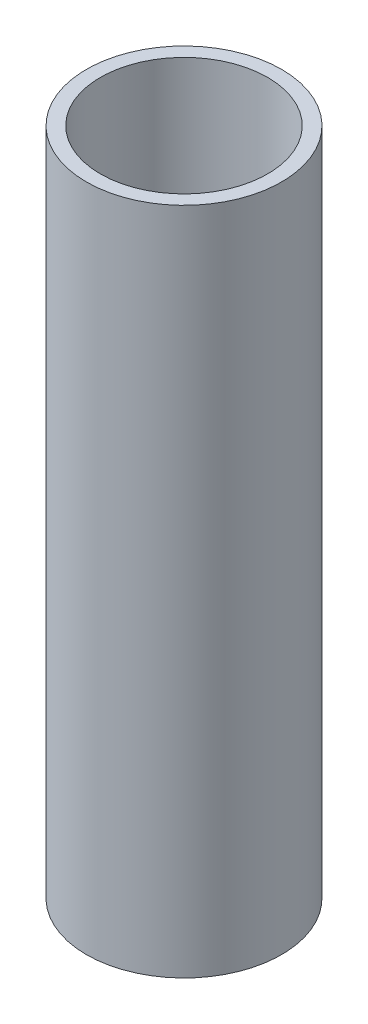
SolidWorks part; units mm, degrees
material "S-Glass Fiber"
ref_plane "Front Plane" through (0, 0, 0) normal (0, 0, 1) x (1, 0, 0)
ref_plane "Top Plane" through (0, 0, 0) normal (0, 1, 0) x (1, 0, 0)
ref_plane "Right Plane" through (0, 0, 0) normal (1, 0, 0) x (0, 0, -1)
sketch "Sketch1" plane through (0, 0, 0) normal (0, 0, 1) x (1, 0, 0)
  line L0 (0, 0) -> (0, -152.4) construction
  line L1 (-22.225, 0) -> (-22.225, -152.4)
  line L2 (-19.05, 0) -> (-19.05, -116.0015)
  line L3 (-19.05, -116.0015) -> (-6.35, -128.7015)
  line L4 (-6.35, -128.7015) -> (-12.7, -152.4)
  line L5 (-19.05, 0) -> (-22.225, 0)
  line L6 (-12.7, -152.4) -> (-22.225, -152.4)
  line L7 (-19.05, 0) -> (0, 0) construction
  point P9 (0, -152.4)
  dimension "D1" = 152.4
  dimension "D2" = 44.45
  dimension "D3" = 38.1
  dimension "D4" = 12.7
  dimension "D5" = 25.4
  dimension "D6" = 45
  dimension "D7" = 15
revolve "body" add sketch "Sketch1" angle 360 about L0
